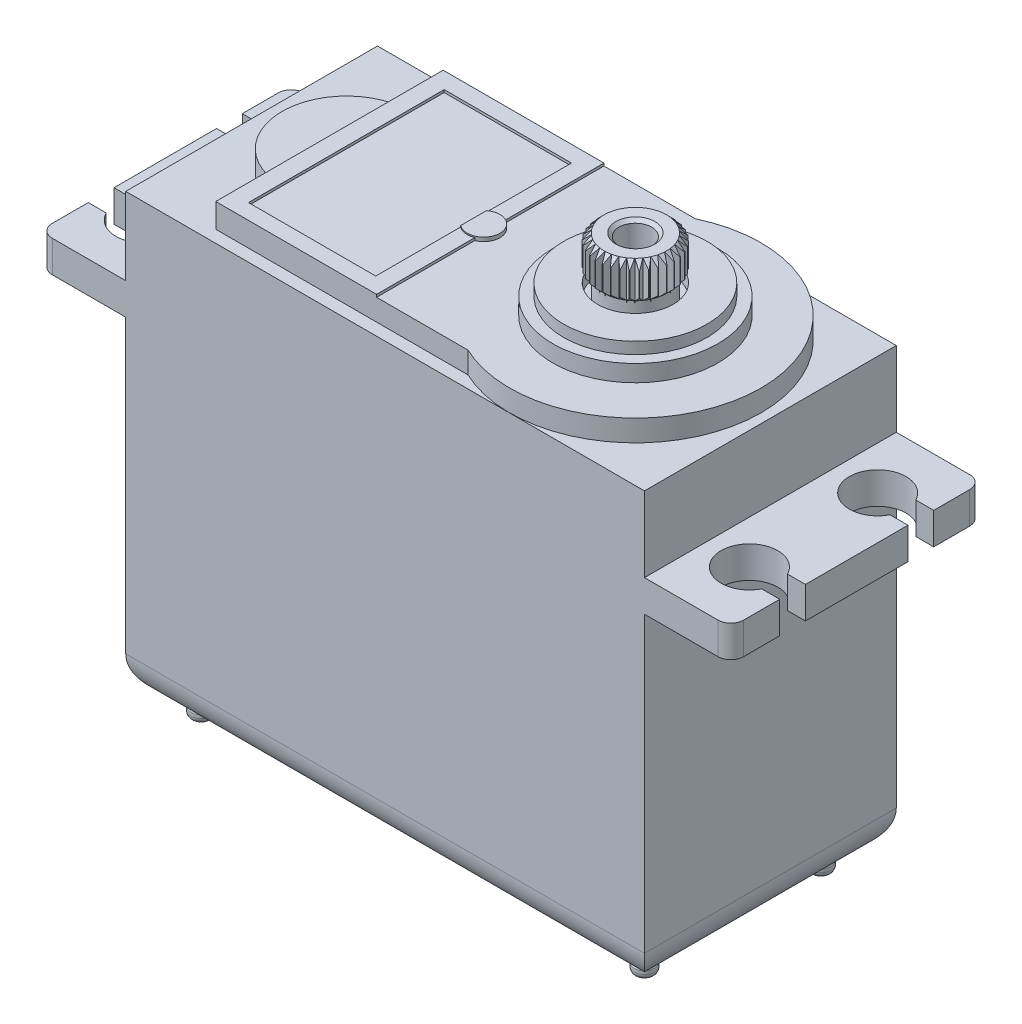
SolidWorks part; units mm, degrees
ref_plane "Front Plane" through (0, 0, 0) normal (0, 0, 1) x (1, 0, 0)
ref_plane "Top Plane" through (0, 0, 0) normal (0, 1, 0) x (1, 0, 0)
ref_plane "Right Plane" through (0, 0, 0) normal (1, 0, 0) x (0, 0, -1)
sketch "Sketch1" plane through (0, 0, 0) normal (0, 1, 0) x (1, 0, 0)
  line L1 (-18.6567, 11.3793) -> (21.6633, 11.3793)
  line L2 (-18.6567, 11.3793) -> (-18.6567, -8.1907)
  line L3 (-18.6567, -8.1907) -> (21.6633, -8.1907)
  line L4 (21.6633, 11.3793) -> (21.6633, -8.1907)
extrude "Boss-Extrude1" add sketch "Sketch1" along normal blind 35.37
sketch "Sketch2" plane through (21.6633, 0, 0) normal (1, 0, 0) x (0, 0, -1)
  line L0 (-8.1907, 0) -> (-8.1907, 3)
  line L1 (-8.1907, 35.37) -> (-8.1907, 0) construction
  line L2 (-8.1907, 3) -> (-5.1907, 0)
  line L3 (-8.1907, 0) -> (11.3793, 0) construction
  line L4 (-5.1907, 0) -> (-8.1907, 0)
  line L5 (1.5943, 0) -> (1.5943, 35.37) construction
  line L6 (-8.1907, 35.37) -> (11.3793, 35.37) construction
  line L7 (8.3793, 0) -> (11.3793, 0)
  line L8 (11.3793, 3) -> (8.3793, 0)
  line L9 (11.3793, 0) -> (11.3793, 3)
extrude "Cut-Extrude1" cut sketch "Sketch2" against normal up to next
sketch "Sketch3" plane through (0, 0, 8.1907) normal (0, 0, 1) x (1, 0, 0)
  line L0 (21.6633, 0) -> (18.6633, 0)
  line L1 (-18.6567, 0) -> (21.6633, 0) construction
  line L2 (18.6633, 0) -> (21.6633, 3)
  line L3 (21.6633, 35.37) -> (21.6633, 3) construction
  line L4 (21.6633, 3) -> (21.6633, 0)
  line L5 (1.5033, 35.37) -> (1.5033, 0) construction
  line L6 (-18.6567, 35.37) -> (21.6633, 35.37) construction
  line L7 (-18.6567, 3) -> (-18.6567, 0)
  line L8 (-15.6567, 0) -> (-18.6567, 3)
  line L9 (-18.6567, 0) -> (-15.6567, 0)
extrude "Cut-Extrude2" cut sketch "Sketch3" against normal up to next
fillet "Fillet2" radius 3 4 edges at (21.6633, 3, -1.5943) (1.5033, 3, 8.1907) (-18.6567, 3, -1.5943) (1.5033, 3, -11.3793)
sketch "Sketch5" plane through (21.6633, 0, 0) normal (1, 0, 0) x (0, 0, -1)
  line L0 (1.5943, 35.37) -> (1.5943, 29.53) construction
  line L1 (-8.1907, 35.37) -> (11.3793, 35.37) construction
  line L2 (-8.1907, 29.53) -> (1.5943, 29.53)
  line L3 (-8.1907, 35.37) -> (-8.1907, 4.2426) construction
  line L4 (1.5943, 29.53) -> (11.3793, 29.53)
  line L5 (11.3793, 35.37) -> (11.3793, 4.2426) construction
  line L6 (11.3793, 29.53) -> (11.3793, 27.07)
  line L7 (11.3793, 27.07) -> (-8.1907, 27.07)
  line L8 (-8.1907, 27.07) -> (-8.1907, 29.53)
extrude "Boss-Extrude2" add sketch "Sketch5" along normal blind 6.71
sketch "Sketch7" plane through (-18.6567, 0, 0) normal (-1, 0, 0) x (0, 0, 1)
  line L0 (-1.5943, 35.37) -> (-1.5943, 29.3613) construction
  line L1 (-11.3793, 29.3613) -> (-1.5943, 29.3613)
  line L2 (-1.5943, 29.3613) -> (8.1907, 29.3613)
  line L3 (8.1907, 29.3613) -> (8.1907, 26.9013)
  line L4 (8.1907, 26.9013) -> (-11.3793, 26.9013)
  line L5 (-11.3793, 26.9013) -> (-11.3793, 29.3613)
  line L6 (-11.3793, 35.37) -> (8.1907, 35.37) construction
  line L7 (8.1907, 35.37) -> (8.1907, 4.2426) construction
  line L8 (-11.3793, 35.37) -> (-11.3793, 4.2426) construction
extrude "Boss-Extrude3" add sketch "Sketch7" along normal blind 6.71
sketch "Sketch8" plane through (0, 29.53, 0) normal (0, 1, 0) x (1, 0, 0)
  line L0 (25.0183, 11.3793) -> (25.0183, 6.5793) construction
  line L1 (28.3733, 11.3793) -> (21.6633, 11.3793) construction
  line L2 (28.3733, 5.5793) -> (26.9779, 5.5793)
  line L3 (25.0183, -8.1907) -> (25.0183, -3.3907) construction
  line L4 (28.3733, -8.1907) -> (21.6633, -8.1907) construction
  line L5 (28.3733, 7.5793) -> (28.3733, 5.5793)
  line L6 (25.0183, 6.5793) -> (28.3733, 6.5793) construction
  line L7 (28.3733, 11.3793) -> (28.3733, -8.1907) construction
  line L8 (28.3733, 6.5793) -> (28.3733, 7.5793) construction
  line L9 (28.3733, 6.5793) -> (28.3733, 5.5793) construction
  line L10 (28.3733, 7.5793) -> (26.9779, 7.5793)
  line L11 (25.0183, -3.3907) -> (28.3733, -3.3907) construction
  line L12 (28.3733, -3.3907) -> (28.3733, -2.3907) construction
  line L13 (28.3733, -3.3907) -> (28.3733, -4.3907) construction
  line L14 (28.3733, -2.3907) -> (26.9779, -2.3907)
  line L15 (28.3733, -4.3907) -> (26.9779, -4.3907)
  line L16 (28.3733, -2.3907) -> (28.3733, -4.3907)
  line L17 (0, 0) -> (1.5, 0) construction
  line L18 (1.5, 0) -> (1.5, -13.7092) construction
  line L19 (-25.3733, -3.3907) -> (-25.3733, -4.3907) construction
  line L20 (-25.3733, -3.3907) -> (-25.3733, -2.3907) construction
  line L21 (-22.0183, -3.3907) -> (-25.3733, -3.3907) construction
  line L22 (-25.3733, 6.5793) -> (-25.3733, 5.5793) construction
  line L23 (-25.3733, 6.5793) -> (-25.3733, 7.5793) construction
  line L24 (-22.0183, 6.5793) -> (-25.3733, 6.5793) construction
  line L25 (-22.0183, -8.1907) -> (-22.0183, -3.3907) construction
  line L26 (-22.0183, 11.3793) -> (-22.0183, 6.5793) construction
  line L27 (-25.3733, -2.3907) -> (-25.3733, -4.3907)
  line L28 (-25.3733, -4.3907) -> (-23.9779, -4.3907)
  line L29 (-25.3733, -2.3907) -> (-23.9779, -2.3907)
  line L30 (-25.3733, 7.5793) -> (-23.9779, 7.5793)
  line L31 (-25.3733, 7.5793) -> (-25.3733, 5.5793)
  line L32 (-25.3733, 5.5793) -> (-23.9779, 5.5793)
  arc A0 (26.9779, 7.5793) -> (26.9779, 5.5793) centre (25.0183, 6.5793) ccw
  arc A1 (26.9779, -2.3907) -> (26.9779, -4.3907) centre (25.0183, -3.3907) ccw
  arc A2 (-23.9779, -2.3907) -> (-23.9779, -4.3907) centre (-22.0183, -3.3907) cw
  arc A3 (-23.9779, 7.5793) -> (-23.9779, 5.5793) centre (-22.0183, 6.5793) cw
extrude "Cut-Extrude3" cut sketch "Sketch8" against normal up to next
sketch "Sketch9" plane through (0, 35.37, 0) normal (0, 1, 0) x (1, 0, 0)
  line L0 (6.9933, -8.1907) -> (6.9933, -7.2426) construction
  line L1 (-18.6567, 6.4311) -> (-12.6067, 6.4311) construction
  line L2 (6.9933, 11.3793) -> (6.9933, 10.4311) construction
  line L3 (-18.6567, -3.2426) -> (-12.6067, -3.2426) construction
  line L4 (-18.6567, -8.1907) -> (-18.6567, 11.3793) construction
  line L5 (-18.6567, 1.5943) -> (21.6633, 1.5943) construction
  line L6 (-12.6067, 10.4311) -> (6.9933, 10.4311)
  line L7 (-18.6567, 11.3793) -> (-18.6567, -8.1907) construction
  line L8 (-12.6067, -7.2426) -> (-12.6067, -3.2426)
  line L9 (21.6633, -8.1907) -> (21.6633, 11.3793) construction
  line L10 (-12.6067, 10.4311) -> (-12.6067, 6.4311)
  line L11 (-12.6067, -7.2426) -> (6.9933, -7.2426)
  line L12 (21.6633, 1.5943) -> (20.9438, 1.5943) construction
  line L13 (21.6633, 11.3793) -> (-18.6567, 11.3793) construction
  arc A0 (6.9933, 10.4311) -> (6.9933, -7.2426) centre (11.1697, 1.5943) cw
  arc A1 (-12.6067, 6.4311) -> (-12.6067, -3.2426) centre (-11.2767, 1.5943) ccw
extrude "Boss-Extrude4" add sketch "Sketch9" along normal blind 1.67
sketch "Sketch10" plane through (0, 37.04, 0) normal (0, 1, 0) x (1, 0, 0)
  circle A1 centre (11.1697, 1.5943) radius 6.415
extrude "Boss-Extrude5" add sketch "Sketch10" along normal blind 1.3
sketch "Sketch11" plane through (0, 38.34, 0) normal (0, 1, 0) x (-1, 0, 0)
  circle A2 centre (-11.1697, -1.5943) radius 5.575
extrude "Boss-Extrude6" add sketch "Sketch11" along normal blind 0.9
sketch "Sketch12" plane through (0, 39.24, 0) normal (0, 1, 0) x (1, 0, 0)
  circle A1 centre (11.1697, 1.5943) radius 2.925
extrude "Cut-Extrude4" cut sketch "Sketch12" against normal blind 1
sketch "Sketch13" plane through (0, 38.24, 0) normal (0, 1, 0) x (-1, 0, 0)
  circle A0 centre (-11.1697, -1.5943) radius 2.425
extrude "Boss-Extrude7" add sketch "Sketch13" along normal blind 1.5
sketch "Sketch14" plane through (0, 39.74, 0) normal (0, 1, 0) x (1, 0, 0)
  circle A0 centre (11.1697, 1.5943) radius 2.925
extrude "Boss-Extrude8" add sketch "Sketch14" along normal blind 2.86
sketch "Sketch15" plane through (0, 42.6, 0) normal (0, 1, 0) x (1, 0, 0)
  circle A0 centre (11.1697, 1.5943) radius 1.27
extrude "Cut-Extrude5" cut sketch "Sketch15" against normal blind 7
sketch "Sketch16" plane through (0, 37.04, 0) normal (0, 1, 0) x (1, 0, 0)
  line L0 (-12.6067, -7.2426) -> (6.9933, -7.2426) construction
  line L1 (-12.6067, 10.4311) -> (-0.1067, 10.4311)
  line L2 (-12.6067, 10.4311) -> (-12.6067, -7.2426)
  line L3 (-12.6067, -7.2426) -> (-0.1067, -7.2426)
  line L4 (-0.1067, 10.4311) -> (-0.1067, -7.2426)
  line L5 (-6.3168, 9.1673) -> (-6.3567, 10.4311) construction
  line L6 (-11.2628, 9.1673) -> (-1.3708, 9.1673)
  line L7 (-11.2628, 9.1673) -> (-11.2628, -6.0433)
  line L8 (-11.2628, -6.0433) -> (-1.3708, -6.0433)
  line L9 (-1.3708, 9.1673) -> (-1.3708, 1.562)
  line L10 (-11.2628, 1.562) -> (-12.6067, 1.5943) construction
  line L11 (-1.3708, 1.562) -> (-0.1067, 1.5943) construction
  line L12 (-6.3168, -6.0433) -> (-6.3567, -7.2426) construction
  line L13 (-1.3708, 1.562) -> (-1.3708, -6.0433)
extrude "Boss-Extrude9" add sketch "Sketch16" along normal blind 0.2
sketch "Sketch17" plane through (0, 37.24, 0) normal (0, 1, 0) x (-1, 0, 0)
  line L0 (1.3708, -1.562) -> (1.3708, -2.562)
  line L1 (1.3708, 6.0433) -> (1.3708, -9.1673) construction
  line L2 (1.3708, -1.562) -> (1.3708, -0.562)
  arc A0 (1.3708, -2.562) -> (1.3708, -0.562) centre (0.592, -1.562) cw
extrude "Boss-Extrude10" add sketch "Sketch17" along normal blind 0.1 and the other way blind 0.5
sketch "Sketch19" plane through (0, 42.6, 0) normal (0, 1, 0) x (1, 0, 0)
  line L0 (10.8404, 4.5007) -> (11.3402, 4.5143) construction
  line L1 (11.3402, 4.5143) -> (11.0903, 4.0075)
  line L2 (11.0903, 4.0075) -> (10.8404, 4.5007)
  line L3 (11.0903, 4.5075) -> (11.0903, 4.0075) construction
  line L4 (10.8404, 4.5007) -> (10.7613, 4.6463)
  line L5 (11.3402, 4.5143) -> (11.4053, 4.6463)
  line L6 (10.7613, 4.6463) -> (11.4053, 4.6463)
  circle A3 centre (11.1697, 1.5943) radius 2.925 construction
  circle A4 centre (11.1697, 1.5943) radius 2.925 construction
extrude "Cut-Extrude11" cut sketch "Sketch19" against normal blind 3
sketch "Sketch21" plane through (0, 0, 0) normal (0, -1, 0) x (1, 0, 0)
  line L0 (1.5033, 5.1907) -> (1.5033, -8.3793) construction
  line L1 (20.7846, 7.3121) -> (17.7846, 7.3121)
  line L2 (20.7846, 7.3121) -> (20.7846, 4.3121)
  line L3 (20.7846, 4.3121) -> (17.7846, 4.3121)
  line L4 (17.7846, 7.3121) -> (17.7846, 4.3121)
  line L5 (-15.6567, 5.1907) -> (18.6633, 5.1907) construction
  line L6 (-15.6567, -8.3793) -> (18.6633, -8.3793) construction
  line L7 (-15.6567, -1.5943) -> (18.6633, -1.5943) construction
  line L8 (-15.6567, -8.3793) -> (-15.6567, 5.1907) construction
  line L9 (18.6633, -8.3793) -> (18.6633, 5.1907) construction
  line L10 (17.7846, -10.5006) -> (17.7846, -7.5006)
  line L11 (20.7846, -7.5006) -> (17.7846, -7.5006)
  line L12 (20.7846, -10.5006) -> (20.7846, -7.5006)
  line L13 (20.7846, -10.5006) -> (17.7846, -10.5006)
  line L14 (-17.778, -7.5006) -> (-14.778, -7.5006)
  line L15 (-14.778, -10.5006) -> (-14.778, -7.5006)
  line L16 (-14.778, 7.3121) -> (-14.778, 4.3121)
  line L17 (-17.778, 4.3121) -> (-14.778, 4.3121)
  line L18 (-17.778, -10.5006) -> (-14.778, -10.5006)
  line L19 (-17.778, -10.5006) -> (-17.778, -7.5006)
  line L20 (-17.778, 7.3121) -> (-17.778, 4.3121)
  line L21 (-17.778, 7.3121) -> (-14.778, 7.3121)
extrude "Cut-Extrude12" cut sketch "Sketch21" against normal blind 1
fillet "Fillet4" radius 1 4 edges at (-14.778, 0.5, -7.5006) (-14.778, 0.5, 4.3121) (17.7846, 0.5, -7.5006) (17.7846, 0.5, 4.3121)
fillet "Fillet5" radius 1 4 edges at (-25.3667, 28.1313, 8.1907) (-25.3667, 28.1313, -11.3793) (28.3733, 28.3, -11.3793) (28.3733, 28.3, 8.1907)
chamfer "Chamfer2" distance 0.5 angle 45 2 edges at (11.2493, 42.6, 1.3297) (11.2493, 39.74, 1.3297)
chamfer "Chamfer3" distance 0.25 angle 45 1 edges at (11.1697, 42.6, -0.3243)
pattern_circular "CirPattern12" count 34 over 360 about axis through (11.1697, 42.6, -1.5943) along (0, -1, 0) of "Cut-Extrude11"
sketch "Sketch23" plane through (0, 1, 0) normal (0, -1, 0) x (1, 0, 0)
  line L0 (1.5033, 5.1907) -> (1.5033, -8.3793) construction
  line L1 (-14.7854, 5.1907) -> (17.792, 5.1907) construction
  line L2 (-14.7854, -8.3793) -> (17.792, -8.3793) construction
  line L3 (18.6633, -1.5943) -> (-15.6567, -1.5943) construction
  line L4 (18.6633, -7.508) -> (18.6633, 4.3195) construction
  line L5 (-15.6567, -7.508) -> (-15.6567, 4.3195) construction
  circle A0 centre (18.7344, -8.4503) radius 0.4237
  circle A1 centre (18.7344, 5.2618) radius 0.4237
  circle A2 centre (-15.7278, 5.2618) radius 0.4237
  circle A3 centre (-15.7278, -8.4503) radius 0.4237
extrude "Boss-Extrude12" add sketch "Sketch23" along normal blind 0.1
sketch "Sketch24" plane through (0, 0.9, 0) normal (0, -1, 0) x (1, 0, 0)
  line L0 (1.5033, 5.1907) -> (1.5033, -8.3793) construction
  line L1 (-14.7854, 5.1907) -> (17.792, 5.1907) construction
  line L2 (-14.7854, -8.3793) -> (17.792, -8.3793) construction
  line L3 (18.6633, -1.5943) -> (-15.6567, -1.5943) construction
  line L4 (18.6633, -7.508) -> (18.6633, 4.3195) construction
  line L5 (-15.6567, -7.508) -> (-15.6567, 4.3195) construction
  circle A0 centre (18.7344, -8.4503) radius 0.8
  circle A1 centre (18.7344, 5.2618) radius 0.8
  circle A2 centre (-15.7278, 5.2618) radius 0.8
  circle A3 centre (-15.7278, -8.4503) radius 0.8
extrude "Boss-Extrude13" add sketch "Sketch24" along normal blind 0.9
fillet "Fillet8" radius 0.45 4 edges at (18.7344, 0, -9.2503) (-15.7278, 0, -7.6503) (-15.7278, 0, 4.4618) (18.7344, 0, 6.0618)
fillet "Fillet9" radius 0.2 4 edges at (-15.7278, 0.9, -7.6503) (-15.7278, 0.9, 4.4618) (18.7344, 0.9, 6.0618) (18.7344, 0.9, -9.2503)
sketch "Sketch25" plane through (0, 0, 0) normal (0, -1, 0) x (1, 0, 0)
  line L0 (18.0844, 5.3868) -> (18.0844, 5.1368)
  line L1 (18.6094, 4.6118) -> (18.8594, 4.6118)
  line L2 (18.0844, 5.3868) -> (18.6094, 5.3868)
  line L3 (18.6094, 5.3868) -> (18.6094, 5.9118)
  line L4 (19.3844, 5.1368) -> (19.3844, 5.3868)
  line L5 (18.8594, 5.9118) -> (18.6094, 5.9118)
  line L6 (1.5033, 5.1907) -> (1.5033, -8.3793) construction
  line L7 (-14.7854, 5.1907) -> (17.792, 5.1907) construction
  line L8 (-14.7854, -8.3793) -> (17.792, -8.3793) construction
  line L9 (18.6633, -1.5943) -> (-15.6567, -1.5943) construction
  line L10 (18.6633, -7.508) -> (18.6633, 4.3195) construction
  line L11 (-15.6567, -7.508) -> (-15.6567, 4.3195) construction
  line L12 (18.6094, -8.3253) -> (18.0844, -8.3253)
  line L13 (18.6094, -7.8003) -> (18.6094, -8.3253)
  line L14 (18.8594, -8.3253) -> (18.8594, -7.8003)
  line L15 (19.3844, -8.3253) -> (18.8594, -8.3253)
  line L16 (18.8594, -8.5753) -> (19.3844, -8.5753)
  line L17 (18.8594, 5.9118) -> (18.8594, 5.3868)
  line L18 (18.8594, 5.3868) -> (19.3844, 5.3868)
  line L19 (18.8594, -9.1003) -> (18.8594, -8.5753)
  line L20 (19.3844, 5.1368) -> (18.8594, 5.1368)
  line L21 (18.8594, 5.1368) -> (18.8594, 4.6118)
  line L22 (18.8594, -9.1003) -> (18.6094, -9.1003)
  line L23 (18.6094, 4.6118) -> (18.6094, 5.1368)
  line L24 (18.6094, 5.1368) -> (18.0844, 5.1368)
  line L25 (19.3844, -8.3253) -> (19.3844, -8.5753)
  line L26 (18.6094, -8.5753) -> (18.6094, -9.1003)
  line L27 (18.0844, -8.5753) -> (18.6094, -8.5753)
  line L28 (18.6094, -7.8003) -> (18.8594, -7.8003)
  line L29 (18.0844, -8.5753) -> (18.0844, -8.3253)
  line L30 (-15.0778, -8.5753) -> (-15.0778, -8.3253)
  line L31 (-15.6028, -7.8003) -> (-15.8528, -7.8003)
  line L32 (-15.0778, -8.5753) -> (-15.6028, -8.5753)
  line L33 (-15.6028, -8.5753) -> (-15.6028, -9.1003)
  line L34 (-16.3778, -8.3253) -> (-16.3778, -8.5753)
  line L35 (-15.6028, 5.1368) -> (-15.0778, 5.1368)
  line L36 (-15.6028, 4.6118) -> (-15.6028, 5.1368)
  line L37 (-15.8528, -9.1003) -> (-15.6028, -9.1003)
  line L38 (-15.8528, 5.1368) -> (-15.8528, 4.6118)
  line L39 (-16.3778, 5.1368) -> (-15.8528, 5.1368)
  line L40 (-15.8528, -9.1003) -> (-15.8528, -8.5753)
  line L41 (-15.8528, 5.3868) -> (-16.3778, 5.3868)
  line L42 (-15.8528, 5.9118) -> (-15.8528, 5.3868)
  line L43 (-15.8528, -8.5753) -> (-16.3778, -8.5753)
  line L44 (-16.3778, -8.3253) -> (-15.8528, -8.3253)
  line L45 (-15.8528, -8.3253) -> (-15.8528, -7.8003)
  line L46 (-15.6028, -7.8003) -> (-15.6028, -8.3253)
  line L47 (-15.6028, -8.3253) -> (-15.0778, -8.3253)
  line L48 (-15.8528, 5.9118) -> (-15.6028, 5.9118)
  line L49 (-16.3778, 5.1368) -> (-16.3778, 5.3868)
  line L50 (-15.6028, 5.3868) -> (-15.6028, 5.9118)
  line L51 (-15.0778, 5.3868) -> (-15.6028, 5.3868)
  line L52 (-15.6028, 4.6118) -> (-15.8528, 4.6118)
  line L53 (-15.0778, 5.3868) -> (-15.0778, 5.1368)
extrude "Cut-Extrude14" cut sketch "Sketch25" against normal blind 0.6
